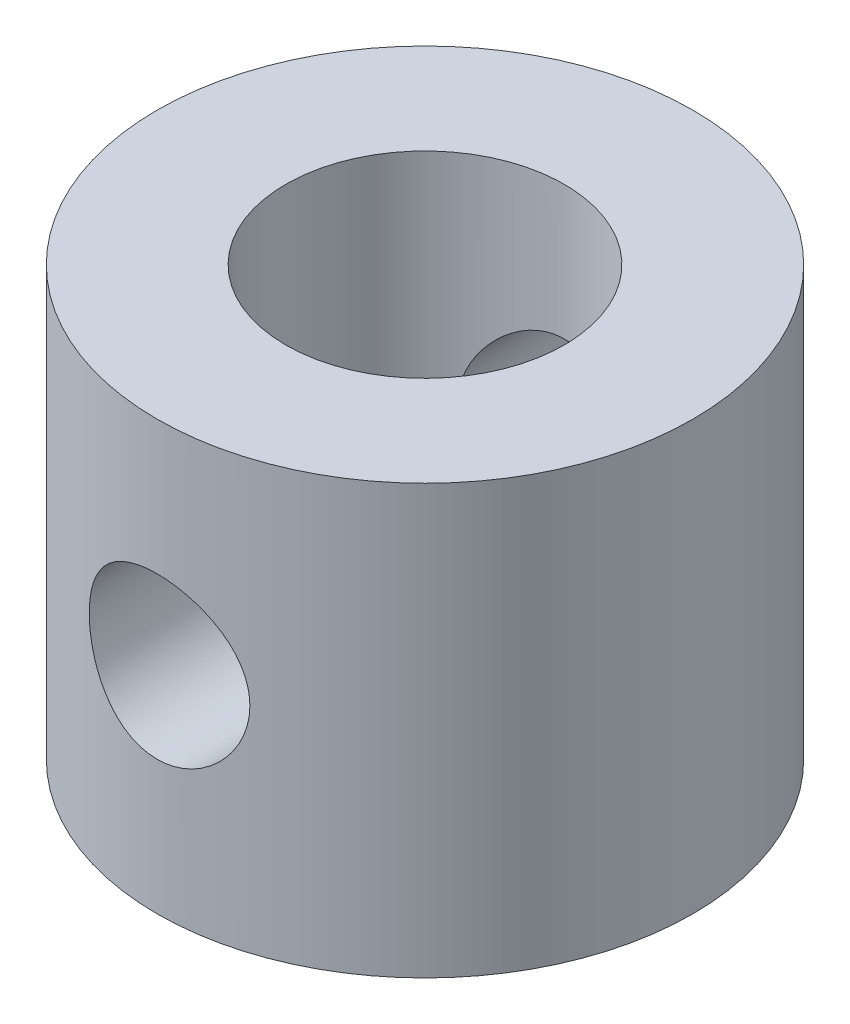
SolidWorks part; units mm, degrees
ref_plane "Front Plane" through (0, 0, 0) normal (0, 0, 1) x (1, 0, 0)
ref_plane "Top Plane" through (0, 0, 0) normal (0, 1, 0) x (1, 0, 0)
ref_plane "Right Plane" through (0, 0, 0) normal (1, 0, 0) x (0, 0, -1)
sketch "Sketch1" plane through (0, 0, 0) normal (0, 1, 0) x (1, 0, 0)
  circle A0 centre (0, 0) radius 5
  dimension "D1" = 10
extrude "Boss-Extrude1" add sketch "Sketch1" along normal blind 8
sketch "Sketch2" plane through (0, 0, 0) normal (0, 1, 0) x (1, 0, 0)
  circle A0 centre (0, 0) radius 2.6
  dimension "D1" = 5.2
extrude "Cut-Extrude1" cut sketch "Sketch2" against normal mid plane 40
sketch "Sketch3" plane through (0, 0, 0) normal (0, 0, 1) x (1, 0, 0)
  circle A0 centre (0, 4) radius 1.5
  dimension "D1" = 3
extrude "Cut-Extrude2" cut sketch "Sketch3" against normal mid plane 40
